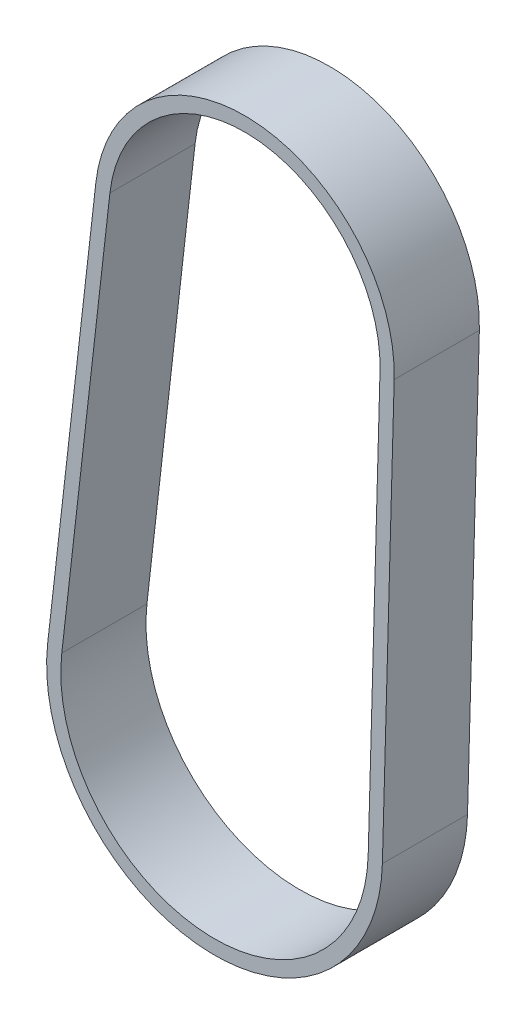
SolidWorks part; units mm, degrees
ref_plane "Front Plane" through (0, 0, 0) normal (0, 0, 1) x (1, 0, 0)
ref_plane "Top Plane" through (0, 0, 0) normal (0, 1, 0) x (1, 0, 0)
ref_plane "Right Plane" through (0, 0, 0) normal (1, 0, 0) x (0, 0, -1)
sketch "Sketch2" plane through (0, 0, 0) normal (0, 0, 1) x (1, 0, 0)
  line L0 (0, 0) -> (1, 0) construction
  line L1 (0, 0) -> (0, 1) construction
  line L4 (-19.3206, -43.0486) -> (-14.2319, 1.6213)
  line L5 (14.3184, -0.3982) -> (13.0687, -45.3395)
  arc A2 (13.0687, -45.3395) -> (-19.3206, -43.0486) centre (-3.175, -44.8879) cw
  arc A3 (-14.2319, 1.6213) -> (14.3184, -0.3982) centre (0, 0) cw
extrude "Extrude-Thin1" add sketch "Sketch2" along normal blind 9 thin thin type one direction wall 1.5
